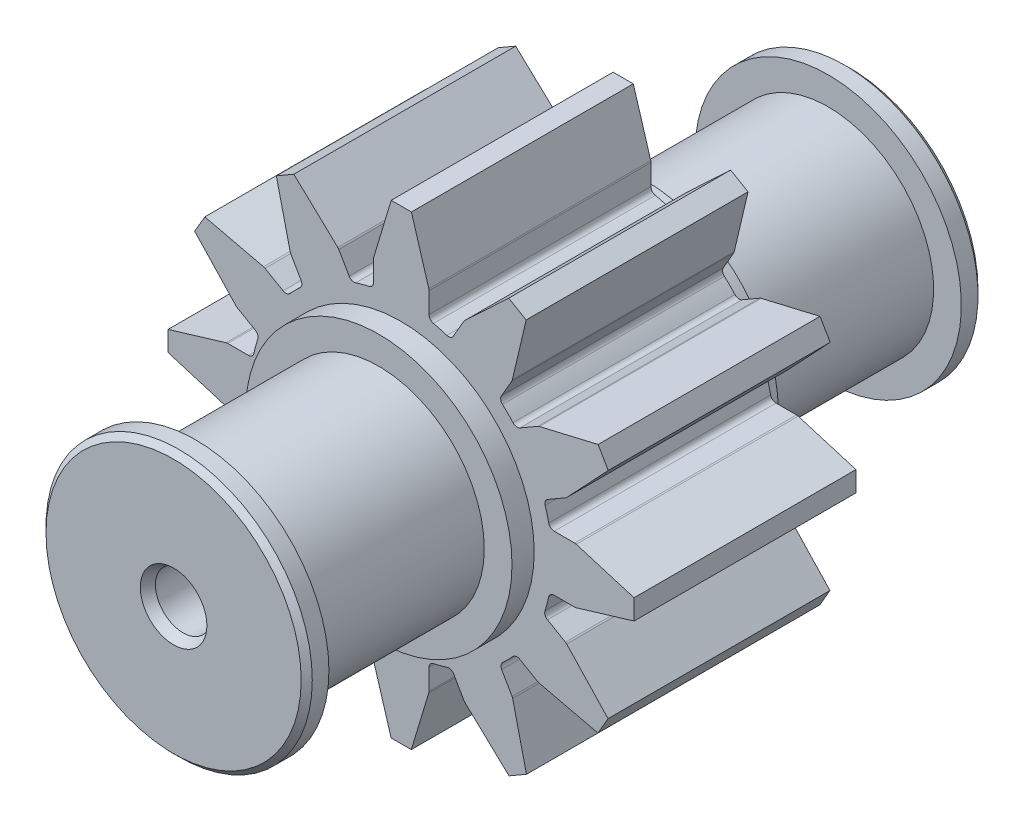
SolidWorks part; units mm, degrees
ref_plane "Спереди" through (0, 0, 0) normal (0, 0, 1) x (1, 0, 0)
ref_plane "Сверху" through (0, 0, 0) normal (0, 1, 0) x (1, 0, 0)
ref_plane "Справа" through (0, 0, 0) normal (1, 0, 0) x (0, 0, -1)
sketch "Эскиз2" plane through (0, 0, 0) normal (0, 0, 1) x (1, 0, 0)
  line L20 (53.7645, -2.946) -> (53.7645, -1.0771)
  line L21 (53.7433, -0.9329) -> (52.1747, 4.2742)
  line L22 (52.1747, 4.2742) -> (50.3546, 4.2742)
  line L23 (50.3546, 4.2742) -> (48.7858, -0.9329)
  line L24 (48.7645, -1.0772) -> (48.7645, -2.9531)
  line L27 (48.7555, -30.4797) -> (48.7555, -32.3473)
  line L28 (48.7768, -32.4916) -> (50.3453, -37.6987)
  line L29 (50.3453, -37.6987) -> (52.1655, -37.6987)
  line L30 (52.1655, -37.6987) -> (53.7343, -32.4916)
  line L31 (53.7555, -32.3473) -> (53.7555, -30.4775)
  line L34 (37.4896, -14.2638) -> (35.6099, -14.2638)
  line L36 (30.2415, -15.8598) -> (30.2586, -17.6738)
  line L37 (30.2586, -17.6738) -> (35.4657, -19.2426)
  line L38 (35.6099, -19.2638) -> (37.5151, -19.2638)
  line L39 (30.2415, -15.8598) -> (35.4656, -14.2851)
  line L41 (65.0289, -19.2139) -> (66.8888, -19.2139)
  line L42 (67.033, -19.1927) -> (72.2401, -17.6241)
  line L43 (72.2401, -17.6241) -> (72.2401, -15.8039)
  line L44 (72.2401, -15.8039) -> (67.033, -14.2352)
  line L45 (66.8887, -14.2139) -> (65.0384, -14.2141)
  line L48 (46.564, -3.5408) -> (45.6287, -1.9209)
  line L49 (45.5382, -1.8066) -> (41.5762, 1.9187)
  line L50 (41.5762, 1.9187) -> (39.9999, 1.0086)
  line L51 (39.9999, 1.0086) -> (41.2449, -4.2853)
  line L52 (41.2986, -4.4209) -> (42.233, -6.0394)
  line L55 (40.6086, -7.6603) -> (38.9805, -6.7203)
  line L56 (38.845, -6.6666) -> (33.5512, -5.4215)
  line L57 (33.5512, -5.4215) -> (32.6411, -6.9978)
  line L58 (32.6411, -6.9978) -> (36.3662, -10.9599)
  line L59 (36.4805, -11.0505) -> (38.0992, -11.985)
  line L62 (38.0961, -21.4251) -> (36.4775, -22.3596)
  line L63 (36.3633, -22.4501) -> (32.638, -26.4121)
  line L64 (32.638, -26.4121) -> (33.5481, -27.9884)
  line L65 (33.5481, -27.9884) -> (38.8378, -26.7444)
  line L66 (38.9806, -26.6864) -> (40.5573, -25.7405)
  line L67 (32.638, -26.4121) -> (36.4137, -22.3964)
  line L69 (42.2473, -27.4181) -> (41.3131, -29.0361)
  line L70 (41.2594, -29.1716) -> (40.0143, -34.4654)
  line L71 (40.0143, -34.4654) -> (41.5906, -35.3755)
  line L72 (41.5906, -35.3755) -> (45.553, -31.6502)
  line L73 (45.6432, -31.5364) -> (46.5897, -29.9013)
  line L76 (55.9807, -29.8805) -> (56.9183, -31.5045)
  line L77 (57.0088, -31.6188) -> (60.9708, -35.344)
  line L78 (60.9708, -35.344) -> (62.5471, -34.434)
  line L79 (62.5471, -34.434) -> (61.3021, -29.1401)
  line L80 (61.2484, -29.0045) -> (60.3134, -27.3849)
  line L83 (61.9386, -25.7577) -> (63.5568, -26.6919)
  line L84 (63.6923, -26.7456) -> (68.9861, -27.9908)
  line L85 (68.9861, -27.9908) -> (69.8962, -26.4145)
  line L86 (69.8962, -26.4145) -> (66.171, -22.4523)
  line L87 (66.0568, -22.3618) -> (64.4371, -21.4267)
  line L90 (64.4528, -12.024) -> (66.0728, -11.0887)
  line L91 (66.1871, -10.9982) -> (69.9123, -7.0362)
  line L92 (69.9123, -7.0362) -> (69.0022, -5.4599)
  line L93 (69.0022, -5.4599) -> (63.7083, -6.7049)
  line L94 (63.5728, -6.7586) -> (61.9545, -7.6929)
  line L97 (60.2872, -6.0251) -> (61.2186, -4.412)
  line L98 (61.2723, -4.2764) -> (62.5174, 1.0174)
  line L99 (62.5174, 1.0174) -> (60.9411, 1.9274)
  line L100 (60.9411, 1.9274) -> (56.979, -1.7977)
  line L101 (56.8884, -1.912) -> (55.9532, -3.5318)
  arc A0 (48.3706, -3.4418) -> (48.7645, -2.9531) centre (48.2645, -2.9531) ccw
  arc A1 (47.1481, -3.7675) -> (46.564, -3.5408) centre (46.997, -3.2908) cw
  arc A2 (48.3706, -3.4418) -> (47.1481, -3.7675) centre (51.2539, -16.7205) ccw
  arc A3 (54.1578, -3.4345) -> (55.3689, -3.7584) centre (51.2539, -16.7205) cw
  arc A4 (60.3845, -6.6456) -> (61.3338, -7.5955) centre (51.2539, -16.7205) cw
  arc A5 (64.2262, -12.6081) -> (64.5499, -13.8206) centre (51.2539, -16.7205) cw
  arc A6 (64.5403, -19.6077) -> (64.2107, -20.8421) centre (51.2539, -16.7205) cw
  arc A7 (61.3184, -25.8547) -> (60.4095, -26.7654) centre (51.2539, -16.7205) cw
  arc A8 (55.3952, -29.6543) -> (54.1489, -29.989) centre (51.2539, -16.7205) cw
  arc A9 (48.362, -29.9912) -> (47.1727, -29.6749) centre (51.2539, -16.7205) cw
  arc A10 (42.1495, -26.7971) -> (41.1853, -25.8337) centre (51.2539, -16.7205) cw
  arc A11 (38.3225, -20.8403) -> (38.0033, -19.6557) centre (51.2539, -16.7205) cw
  arc A12 (37.9785, -13.8689) -> (38.3253, -12.5708) centre (51.2539, -16.7205) cw
  arc A13 (41.2278, -7.5645) -> (42.1358, -6.6599) centre (51.2539, -16.7205) cw
  arc A14 (54.1578, -3.4345) -> (53.7645, -2.946) centre (54.2645, -2.946) cw
  arc A15 (55.3689, -3.7584) -> (55.9532, -3.5318) centre (55.5202, -3.2818) ccw
  arc A16 (60.3845, -6.6456) -> (60.2872, -6.0251) centre (60.7202, -6.2751) cw
  arc A17 (61.9545, -7.6929) -> (61.3338, -7.5955) centre (61.7045, -7.2599) cw
  arc A18 (56.979, -1.7977) -> (56.8884, -1.912) centre (57.3215, -2.162) ccw
  arc A19 (53.7433, -0.9329) -> (53.7645, -1.0771) centre (53.2645, -1.0771) cw
  arc A20 (48.7858, -0.9329) -> (48.7645, -1.0772) centre (49.2645, -1.0772) ccw
  arc A21 (45.5382, -1.8066) -> (45.6287, -1.9209) centre (45.1957, -2.1709) cw
  arc A22 (63.5728, -6.7586) -> (63.7083, -6.7049) centre (63.8228, -7.1916) cw
  arc A23 (61.2723, -4.2764) -> (61.2186, -4.412) centre (60.7856, -4.162) cw
  arc A24 (64.5499, -13.8206) -> (65.0384, -14.2141) centre (65.0384, -13.7141) ccw
  arc A25 (64.2262, -12.6081) -> (64.4528, -12.024) centre (64.7028, -12.457) cw
  arc A26 (66.8887, -14.2139) -> (67.033, -14.2352) centre (66.8888, -14.7139) cw
  arc A27 (66.1871, -10.9982) -> (66.0728, -11.0887) centre (65.8228, -10.6557) cw
  arc A28 (64.5403, -19.6077) -> (65.0289, -19.2139) centre (65.0289, -19.7139) cw
  arc A29 (67.033, -19.1927) -> (66.8888, -19.2139) centre (66.8888, -18.7139) cw
  arc A30 (64.4371, -21.4267) -> (64.2107, -20.8421) centre (64.6871, -20.9937) cw
  arc A31 (66.171, -22.4523) -> (66.0568, -22.3618) centre (65.8068, -22.7948) ccw
  arc A32 (61.3184, -25.8547) -> (61.9386, -25.7577) centre (61.6886, -26.1907) cw
  arc A33 (63.6923, -26.7456) -> (63.5568, -26.6919) centre (63.8068, -26.2589) cw
  arc A34 (60.3134, -27.3849) -> (60.4095, -26.7654) centre (60.7464, -27.1349) cw
  arc A35 (61.3021, -29.1401) -> (61.2484, -29.0045) centre (60.8154, -29.2545) ccw
  arc A36 (56.9183, -31.5045) -> (57.0088, -31.6188) centre (57.3513, -31.2545) ccw
  arc A37 (55.9807, -29.8805) -> (55.3952, -29.6543) centre (55.5477, -30.1305) ccw
  arc A38 (53.7555, -30.4775) -> (54.1489, -29.989) centre (54.2555, -30.4775) cw
  arc A39 (53.7343, -32.4916) -> (53.7555, -32.3473) centre (53.2555, -32.3473) ccw
  arc A40 (48.7555, -32.3473) -> (48.7768, -32.4916) centre (49.2555, -32.3473) ccw
  arc A41 (48.362, -29.9912) -> (48.7555, -30.4797) centre (48.2555, -30.4797) cw
  arc A42 (46.5897, -29.9013) -> (47.1727, -29.6749) centre (47.0224, -30.1518) cw
  arc A43 (45.553, -31.6502) -> (45.6432, -31.5364) centre (45.2105, -31.2859) ccw
  arc A44 (41.3131, -29.0361) -> (41.2594, -29.1716) centre (41.7462, -29.2861) ccw
  arc A45 (42.1495, -26.7971) -> (42.2473, -27.4181) centre (41.8143, -27.1681) cw
  arc A46 (41.1853, -25.8337) -> (40.5573, -25.7405) centre (40.8145, -26.1692) ccw
  arc A47 (38.8378, -26.7444) -> (38.9806, -26.6864) centre (38.7234, -26.2577) ccw
  arc A48 (36.4775, -22.3596) -> (36.3633, -22.4501) centre (36.7275, -22.7926) ccw
  arc A49 (38.0961, -21.4251) -> (38.3225, -20.8403) centre (37.8461, -20.9921) ccw
  arc A50 (37.5151, -19.2638) -> (38.0033, -19.6557) centre (37.5151, -19.7638) cw
  arc A51 (35.4657, -19.2426) -> (35.6099, -19.2638) centre (35.6099, -18.7638) ccw
  arc A52 (35.4656, -14.2851) -> (35.6099, -14.2638) centre (35.6099, -14.7638) cw
  arc A53 (37.9785, -13.8689) -> (37.4896, -14.2638) centre (37.4896, -13.7638) cw
  arc A54 (38.0992, -11.985) -> (38.3253, -12.5708) centre (37.8492, -12.418) cw
  arc A55 (36.3662, -10.9599) -> (36.4805, -11.0505) centre (36.7305, -10.6175) ccw
  arc A56 (38.9805, -6.7203) -> (38.845, -6.6666) centre (38.7305, -7.1534) ccw
  arc A57 (41.2278, -7.5645) -> (40.6086, -7.6603) centre (40.8586, -7.2273) cw
  arc A58 (42.233, -6.0394) -> (42.1358, -6.6599) centre (41.8, -6.2894) cw
  arc A59 (41.2449, -4.2853) -> (41.2986, -4.4209) centre (41.7316, -4.1709) ccw
extrude "Вытянуть1" add sketch "Эскиз2" along normal blind 20 contours L63 A48 L62 A49 A11 A50 L38 A51 L37 L36 L39 A52 L34 A53 A12 A54 L59 A55 L58 L57 L56 A56 L55 A57 A13 A58 L52 A59 L51 L50 L49 A21 L48 A1 A2 A0 L24 A20 L23 L22 L21 A19 L20 A14 A3 A15 L101 A18 L100 L99 L98 A23 L97 A16 A4 A17 L94 A22 L93 L92 L91 A27 L90 A25 A5 A24 L45 A26 L44 L43 L42 A29 L41 A28 A6 A30 L87 A31 L86 L85 L84 A33 L83 A32 A7 A34 L80 A35 L79 L78 L77 A36 L76 A37 A8 A38 L31 A39 L30 L29 L28 A40 L27 A41 A9 A42 L73 A43 L72 L71 L70 A44 L69 A45 A10 A46 L66 A47 L65 L64
sketch "Эскиз3" plane through (0, 0, 0) normal (0, 0, -1) x (-1, 0, 0)
  line L0 (-72.2401, -17.6241) -> (-72.2401, -15.8039) construction
  line L1 (-30.2415, -15.8598) -> (-30.2586, -17.6738) construction
  circle A0 centre (-51.2401, -16.7331) radius 12
  point P2 (-72.2401, -16.714)
  point P7 (-72.2401, -16.714)
  dimension "D1" = 41.9887
  dimension "D2" = 21
extrude "Вытянуть2" add sketch "Эскиз3" along normal blind 2
sketch "Эскиз4" plane through (0, 0, 20) normal (0, 0, 1) x (1, 0, 0)
  circle A0 centre (51.2401, -16.7331) radius 12
extrude "Вытянуть3" add sketch "Эскиз4" along normal blind 2
sketch "Эскиз5" plane through (0, 0, -2) normal (0, 0, -1) x (-1, 0, 0)
  circle A0 centre (-51.2401, -16.7331) radius 9.5
extrude "Вытянуть4" add sketch "Эскиз5" along normal blind 16.5
sketch "Эскиз6" plane through (0, 0, -18.5) normal (0, 0, -1) x (-1, 0, 0)
  circle A0 centre (-51.2401, -16.7331) radius 12
extrude "Вытянуть5" add sketch "Эскиз6" along normal blind 2
chamfer "Фаска2" distance 0.5 angle 45 1 edges at (39.2401, -16.7331, -20.5)
sketch "Эскиз7" plane through (0, 0, 22) normal (0, 0, 1) x (1, 0, 0)
  circle A0 centre (51.2401, -16.7331) radius 9.5
extrude "Вытянуть6" add sketch "Эскиз7" along normal blind 16.5
sketch "Эскиз8" plane through (0, 0, 38.5) normal (0, 0, 1) x (1, 0, 0)
  circle A0 centre (51.2401, -16.7331) radius 12
extrude "Вытянуть7" add sketch "Эскиз8" along normal blind 2
chamfer "Фаска3" distance 0.5 angle 45 1 edges at (63.2401, -16.7331, 40.5)
sketch "Эскиз15" plane through (0, 0, -20.5) normal (0, 0, -1) x (-1, 0, 0)
  circle A0 centre (-51.2401, -16.7331) radius 2.5
extrude "Вытянуть13" cut sketch "Эскиз15" against normal blind 74
chamfer "Фаска6" distance 0.5 angle 60 1 edges at (48.7401, -16.7331, -20.5) first distance on face at (48.7401, -16.7331, -20.5)
chamfer "Фаска9" distance 0.5 angle 60 1 edges at (53.7401, -16.7331, 40.5) first distance on face at (53.7401, -16.7331, 40.5)
